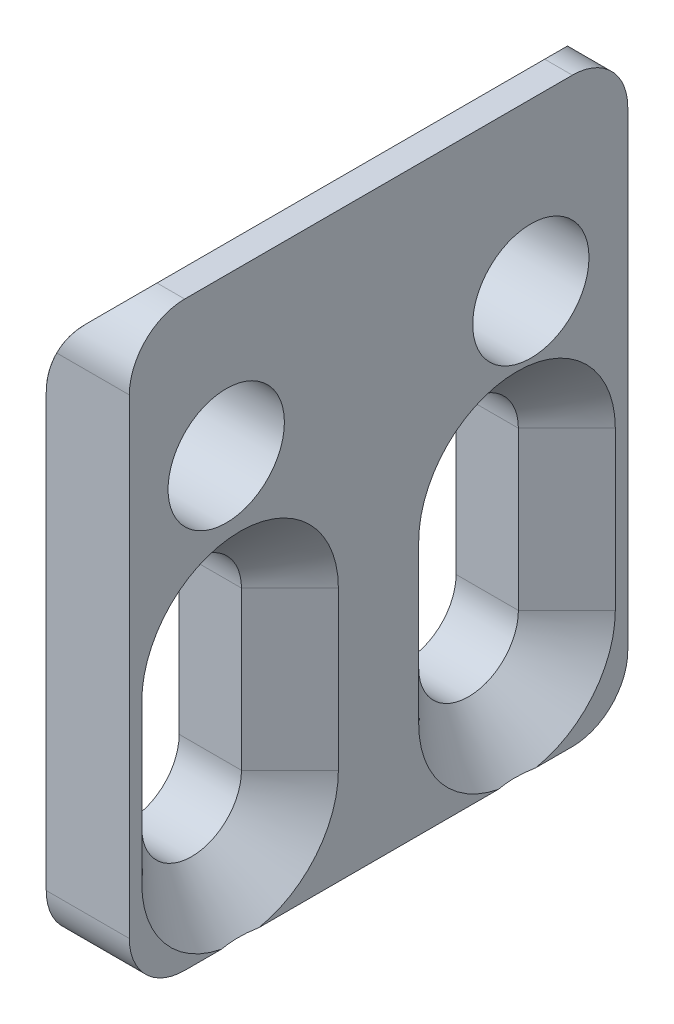
SolidWorks part; units mm, degrees
ref_plane "Front Plane" through (0, 0, 0) normal (0, 0, 1) x (1, 0, 0)
ref_plane "Top Plane" through (0, 0, 0) normal (0, 1, 0) x (1, 0, 0)
ref_plane "Right Plane" through (0, 0, 0) normal (1, 0, 0) x (0, 0, -1)
sketch "Sketch1" plane through (0, 0, 0) normal (1, 0, 0) x (0, 0, -1)
  line L1 (-9, 10.5) -> (9, 10.5)
  line L2 (-9, 10.5) -> (-9, -10.5)
  line L3 (-9, -10.5) -> (9, -10.5)
  line L4 (9, 10.5) -> (9, -10.5)
  line L5 (-9, 10.5) -> (9, -10.5) construction
  line L6 (-9, -10.5) -> (9, 10.5) construction
  circle A0 centre (5.5, 4.5) radius 2.1
  circle A1 centre (-5.5, 4.8462) radius 2.1
  point P0 (0, 0)
  dimension "D4" = 4.2
  dimension "D1" = 18
  dimension "D2" = 21
  dimension "D3" = 6
  dimension "D5" = 11
  dimension "D6" = 5.5
extrude "Boss-Extrude1" add sketch "Sketch1" along normal blind 4
sketch "Sketch2" plane through (4, 0, 0) normal (1, 0, 0) x (0, 0, -1)
  line L0 (5, -1.3165) -> (5, -7.0148) construction
  line L1 (6.8, -1.3165) -> (6.8, -7.0148)
  line L2 (3.2, -1.3165) -> (3.2, -7.0148)
  line L3 (-5, -1.3165) -> (-5, -7.0148) construction
  line L4 (-3.2, -1.3165) -> (-3.2, -7.0148)
  line L5 (-6.8, -1.3165) -> (-6.8, -7.0148)
  arc A0 (6.8, -1.3165) -> (3.2, -1.3165) centre (5, -1.3165) ccw
  arc A1 (3.2, -7.0148) -> (6.8, -7.0148) centre (5, -7.0148) ccw
  arc A2 (-3.2, -1.3165) -> (-6.8, -1.3165) centre (-5, -1.3165) ccw
  arc A3 (-6.8, -7.0148) -> (-3.2, -7.0148) centre (-5, -7.0148) ccw
  point P2 (5, -4.1656)
  point P7 (-5, -4.1656)
  point P14 (0, 0)
  point P15 (5, -1.1096)
  point P17 (5, -7.2593)
  point P18 (0, 0)
  point P19 (0, 0)
  point P20 (5, -1.3165)
  dimension "D2" = 1.8
  dimension "D1" = 10
  dimension "D3" = 5
extrude "Cut-Extrude1" cut sketch "Sketch2" against normal blind 4
chamfer "Chamfer1" distance 1.75 angle 45 8 edges at (4, -8.8148, -5) (4, -4.1656, -6.8) (4, -4.1656, -3.2) (4, 0.4835, -5) (4, -8.8148, 5) (4, -4.1656, 3.2) (4, -4.1656, 6.8) (4, 0.4835, 5)
fillet "Fillet1" radius 2 4 edges at (2, 10.5, -9) (2, -10.5, -9) (2, -10.5, 9) (2, 10.5, 9)
chamfer "Chamfer2" distance 3 angle 45 1 edges at (0, 10.5, 0) tangent propagation no
chamfer "Chamfer3" distance 1 angle 45 5 edges at (0, -0.5, -9) (0, -9.9142, -8.4142) (0, -10.5, 0) (0, -9.9142, 8.4142) (0, -0.5, 9)
fillet "Fillet2" radius 2 2 edges at (0.5, 8, -8.5) (0.5, 8, 8.5)
